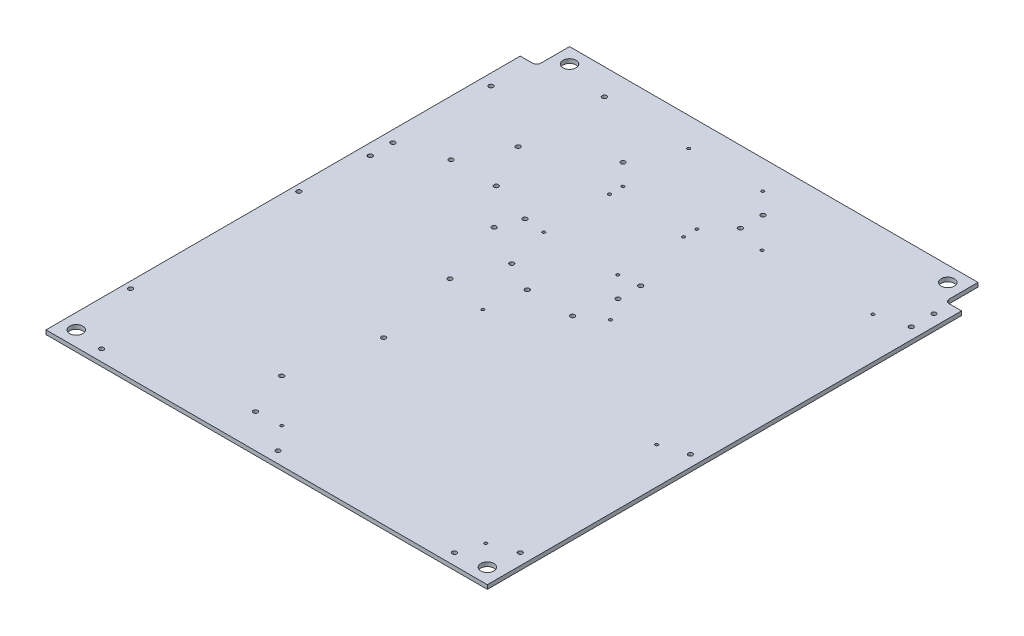
SolidWorks part; units mm, degrees
ref_plane "Front" through (0, 0, 0) normal (0, 0, 1) x (1, 0, 0)
ref_plane "Top" through (0, 0, 0) normal (0, 1, 0) x (1, 0, 0)
ref_plane "Right" through (0, 0, 0) normal (1, 0, 0) x (0, 0, -1)
sketch "Sketch1" plane through (0, 0, 0) normal (0, 1, 0) x (1, 0, 0)
  line L1 (170.434, -195.834) -> (-170.434, -195.834)
  line L2 (170.434, -195.834) -> (170.434, 195.834)
  line L3 (170.434, 195.834) -> (-170.434, 195.834)
  line L4 (-170.434, -195.834) -> (-170.434, 195.834)
  line L5 (170.434, -195.834) -> (-170.434, 195.834) construction
  line L6 (170.434, 195.834) -> (-170.434, -195.834) construction
  point P0 (0, 0)
  dimension "D1" = 340.868
  dimension "D2" = 391.668
extrude "Boss-Extrude1" add sketch "Sketch1" along normal blind 3.175
sketch "Sketch2" plane through (0, 3.175, 0) normal (0, 1, 0) x (1, 0, 0)
  line L0 (170.434, 195.834) -> (-170.434, 195.834) construction
  line L1 (-170.434, 195.834) -> (-157.734, 195.834)
  line L2 (-170.434, 195.834) -> (-170.434, 170.434)
  line L3 (-170.434, 170.434) -> (-160.909, 170.434)
  line L4 (-157.734, 195.834) -> (-157.734, 173.609)
  line L5 (170.434, 195.834) -> (157.734, 195.834)
  line L6 (170.434, 195.834) -> (170.434, 170.434)
  line L7 (170.434, 170.434) -> (160.909, 170.434)
  line L8 (157.734, 195.834) -> (157.734, 173.609)
  arc A0 (-157.734, 173.609) -> (-160.909, 170.434) centre (-160.909, 173.609) cw
  arc A1 (157.734, 173.609) -> (160.909, 170.434) centre (160.909, 173.609) ccw
  dimension "D1" = 3.175
  dimension "D2" = 25.4
  dimension "D3" = 12.7
extrude "Cut-Extrude1" cut sketch "Sketch2" against normal blind 10
hole_wizard "3/8 Clearance Hole1" positions "Sketch3" profile "Sketch4" hole size "3/8" standard "ANSI Inch" end condition through all
sketch "Sketch3" plane through (0, 3.175, 0) normal (0, 1, 0) x (1, 0, 0)
  line L0 (158.75, -184.15) -> (0, -184.15) construction
  line L1 (0, -184.15) -> (-158.75, -184.15) construction
  line L2 (-158.75, -184.15) -> (-158.75, -12.7) construction
  line L3 (-158.75, -12.7) -> (-158.75, 158.75) construction
  line L4 (-158.75, 158.75) -> (158.75, 158.75) construction
  line L5 (158.75, 158.75) -> (158.75, -12.7) construction
  line L6 (158.75, -12.7) -> (158.75, -184.15) construction
  line L8 (146.05, 184.15) -> (0, 184.15) construction
  line L9 (0, 184.15) -> (-146.05, 184.15) construction
  line L10 (-146.05, 184.15) -> (-157.734, 195.834) construction
  line L12 (157.734, 195.834) -> (146.05, 184.15) construction
  line L14 (-158.75, 158.75) -> (-170.434, 170.434) construction
  line L16 (-158.75, -184.15) -> (-170.434, -195.834) construction
  line L18 (158.75, 158.75) -> (170.434, 170.434) construction
  line L20 (158.75, -184.15) -> (170.434, -195.834) construction
  line L21 (158.75, -184.15) -> (158.75, -195.834) construction
  line L22 (-170.434, -195.834) -> (170.434, -195.834) construction
  line L24 (158.75, -184.15) -> (170.434, -184.15) construction
  line L25 (170.434, -195.834) -> (170.434, 170.434) construction
  point P0 (158.75, -184.15)
  point P2 (-158.75, -184.15)
  point P94 (-146.05, 184.15)
  point P96 (146.05, 184.15)
  dimension "D1" = 11.684
sketch "Sketch4" plane through (158.75, 3.175, 184.15) normal (1, 0, 0) x (0, 0, 1)
  line L0 (0, 0) -> (0, 3.175)
  line L1 (0, 3.175) -> (5.0419, 3.175)
  line L2 (5.0419, 3.175) -> (5.0419, 0)
  line L5 (5.0419, 0) -> (0, 0)
  line L11 (0, -6.35) -> (0, 107.95) construction
  dimension "Thru Hole Dia." = 10.0838
  dimension "Thru Hole Depth" = 3.175
hole_wizard "#4-40 Tapped Hole1" positions "Sketch5" profile "Sketch6" tap size "#4-40" standard "ANSI Inch" end condition through all
sketch "Sketch5" plane through (0, 3.175, 0) normal (0, 1, 0) x (1, 0, 0)
  point P0 (-15.34, -13.51)
  point P3 (142.14, -36.73)
  point P6 (142.14, -168.81)
  point P9 (-15.34, -168.81)
  point P12 (-43.575, 61.759)
  point P15 (13.575, 61.759)
  point P18 (13.575, 112.559)
  point P21 (-43.575, 112.559)
  point P24 (-43.575, 122.909)
  point P27 (-43.575, 173.709)
  point P30 (13.575, 173.709)
  point P33 (13.575, 122.909)
cosmetic thread "Hole Thread1" parameters "D2"=2.8448
cosmetic thread "Hole Thread2" parameters "D2"=2.8448
cosmetic thread "Hole Thread3" parameters "D2"=2.8448
cosmetic thread "Hole Thread4" parameters "D2"=2.8448
cosmetic thread "Hole Thread9" parameters "D2"=2.8448
cosmetic thread "Hole Thread10" parameters "D2"=2.8448
cosmetic thread "Hole Thread11" parameters "D2"=2.8448
cosmetic thread "Hole Thread12" parameters "D2"=2.8448
cosmetic thread "Hole Thread13" parameters "D2"=2.8448
cosmetic thread "Hole Thread14" parameters "D2"=2.8448
cosmetic thread "Hole Thread15" parameters "D2"=2.8448
cosmetic thread "Hole Thread16" parameters "D2"=2.8448
sketch "Sketch6" plane through (-15.34, 3.175, 13.51) normal (1, 0, 0) x (0, 0, 1)
  line L0 (0, 0) -> (0, 3.175)
  line L1 (0, 3.175) -> (1.1303, 3.175)
  line L2 (1.1303, 3.175) -> (1.1303, 0)
  line L5 (1.1303, 0) -> (0, 0)
  line L11 (0, -6.35) -> (0, 107.95) construction
  dimension "Thru Tap Drill Dia." = 2.2606
  dimension "Thru Tap Drill Depth" = 3.175
hole_wizard "#8-32 Tapped Hole1" positions "Sketch7" profile "Sketch8" tap size "#8-32" standard "ANSI Inch" end condition through all
sketch "Sketch7" plane through (0, 3.175, 0) normal (0, 1, 0) x (1, 0, 0)
  arc A0 (-165.334, -7.875) -> (-165.334, -3.375) centre (-165.334, -5.625) ccw construction
  arc A1 (-165.334, -137.875) -> (-165.334, -133.375) centre (-165.334, -135.625) ccw construction
  arc A2 (-48.634, -3.375) -> (-48.634, -7.875) centre (-48.634, -5.625) ccw construction
  arc A3 (-48.634, -133.375) -> (-48.634, -137.875) centre (-48.634, -135.625) ccw construction
  point P0 (-165.334, -5.625)
  point P2 (-165.334, -135.625)
  point P5 (-48.634, -135.625)
  point P9 (-48.634, -5.625)
cosmetic thread "Hole Thread5" parameters "D2"=4.1656
cosmetic thread "Hole Thread6" parameters "D2"=4.1656
cosmetic thread "Hole Thread7" parameters "D2"=4.1656
cosmetic thread "Hole Thread8" parameters "D2"=4.1656
sketch "Sketch8" plane through (-165.334, 3.175, 5.625) normal (1, 0, 0) x (0, 0, 1)
  line L0 (0, 0) -> (0, 3.175)
  line L1 (0, 3.175) -> (1.7272, 3.175)
  line L2 (1.7272, 3.175) -> (1.7272, 0)
  line L5 (1.7272, 0) -> (0, 0)
  line L11 (0, -6.35) -> (0, 107.95) construction
  dimension "Thru Tap Drill Dia." = 3.4544
  dimension "Thru Tap Drill Depth" = 3.175
hole_wizard "#4-40 Tapped Hole2" positions "Sketch9" profile "Sketch10" tap size "#4-40" standard "ANSI Inch" end condition through all
sketch "Sketch9" plane through (0, 3.175, 0) normal (0, 1, 0) x (1, 0, 0)
  circle A0 centre (52.859, 133.909) radius 1.6319 construction
  circle A1 centre (138.509, 133.909) radius 1.6319 construction
  point P4 (138.509, 133.909)
  point P6 (52.859, 133.909)
  point P20 (40.864, 28.904)
cosmetic thread "Hole Thread17" parameters "D2"=2.8448
cosmetic thread "Hole Thread18" parameters "D2"=2.8448
sketch "Sketch10" plane through (138.509, 3.175, -133.909) normal (1, 0, 0) x (0, 0, 1)
  line L0 (0, 0) -> (0, 3.175)
  line L1 (0, 3.175) -> (1.1303, 3.175)
  line L2 (1.1303, 3.175) -> (1.1303, 0)
  line L5 (1.1303, 0) -> (0, 0)
  line L11 (0, -6.35) -> (0, 107.95) construction
  dimension "Thru Tap Drill Dia." = 2.2606
  dimension "Thru Tap Drill Depth" = 3.175
cosmetic thread "Hole Thread19" parameters "D2"=2.8448
hole_wizard "#8-32 Tapped Hole2" positions "Sketch13" profile "Sketch14" tap size "#8-32" standard "ANSI Inch" end condition through all
sketch "Sketch13" plane through (0, 3.175, 0) normal (0, 1, 0) x (1, 0, 0)
  line L0 (-92.8222, 74.3083) -> (-127.8222, 74.3083)
  line L2 (-170.434, 170.434) -> (-170.434, -195.834) construction
  line L3 (-170.434, 170.434) -> (-160.909, 170.434) construction
  line L4 (-161.684, 139.084) -> (-161.684, 45.834)
  line L6 (-170.434, 170.434) -> (-170.434, -195.834) construction
  line L7 (161.684, 157.834) -> (161.684, -161.684)
  line L9 (170.434, -195.834) -> (170.434, 170.434) construction
  line L10 (29.684, 157.834) -> (29.684, 45.834)
  line L12 (-161.684, 45.834) -> (29.684, 45.834)
  line L14 (-59.684, 139.084) -> (-59.684, 45.834)
  line L16 (-34.884, 45.834) -> (-34.884, -187.084)
  line L18 (-136.284, -187.084) -> (136.284, -187.084)
  line L20 (136.284, -187.084) -> (161.684, -187.084)
  line L21 (161.684, -187.084) -> (161.684, -161.684)
  line L22 (-170.434, -195.834) -> (170.434, -195.834) construction
  line L23 (157.734, 195.834) -> (-157.734, 195.834) construction
  line L24 (29.684, 157.834) -> (161.684, 157.834)
  line L26 (29.684, 140.334) -> (161.684, 140.334) construction
  line L28 (-161.684, 63.334) -> (29.684, 63.334) construction
  line L30 (-110.684, 175.684) -> (-110.684, 109.084)
  line L31 (-34.884, -169.584) -> (-34.884, 28.334) construction
  line L33 (-11.384, 16.834) -> (23.616, 16.834)
  point P0 (-127.8222, 74.3083)
  point P2 (-92.8222, 74.3083)
  point P14 (-59.684, 139.084)
  point P16 (-59.684, 63.334)
  point P18 (-161.684, 45.834)
  point P20 (-161.684, 63.334)
  point P22 (-161.684, 139.084)
  point P24 (29.684, 45.834)
  point P26 (29.684, 63.334)
  point P28 (29.684, 140.334)
  point P30 (29.684, 157.834)
  point P32 (161.684, 157.834)
  point P34 (161.684, 140.334)
  point P36 (161.684, -161.684)
  point P38 (161.684, -30.2348)
  point P40 (136.284, -187.084)
  point P42 (0, -187.084)
  point P44 (-136.284, -187.084)
  point P46 (-34.884, -169.584)
  point P48 (-34.884, 28.334)
  point P50 (-34.884, -70.625)
  point P52 (-66, 45.834)
  point P124 (-110.684, 175.684)
  point P126 (-110.684, 109.084)
  point P143 (-11.384, 16.834)
  point P145 (23.616, 16.834)
  dimension "D1" = 35
  dimension "D2" = 42.6118
  dimension "D3" = 96.1257
  dimension "D4" = 8.75
  dimension "D5" = 8.75
  dimension "D6" = 25.4
  dimension "D7" = 25.4
  dimension "D8" = 8.75
  dimension "D9" = 56.75
  dimension "D10" = 102
  dimension "D11" = 38
  dimension "D12" = 17.5
  dimension "D13" = 17.5
  dimension "D14" = 132
  dimension "D15" = 112
  dimension "D16" = 126.8
  dimension "D17" = 20.15
  dimension "D18" = 66.6
  dimension "D19" = 59.75
  dimension "D20" = 17.5
  dimension "D21" = 17.5
  dimension "D22" = 29
  dimension "D23" = 23.5
sketch "Sketch14" plane through (-127.8222, 3.175, -74.3083) normal (1, 0, 0) x (0, 0, 1)
  line L0 (0, 0) -> (0, 3.175)
  line L1 (0, 3.175) -> (1.7272, 3.175)
  line L2 (1.7272, 3.175) -> (1.7272, 0)
  line L5 (1.7272, 0) -> (0, 0)
  line L11 (0, -6.35) -> (0, 107.95) construction
  dimension "Thread Major Dia." = 3.4544
  dimension "Thru Tap Drill Depth" = 3.175
